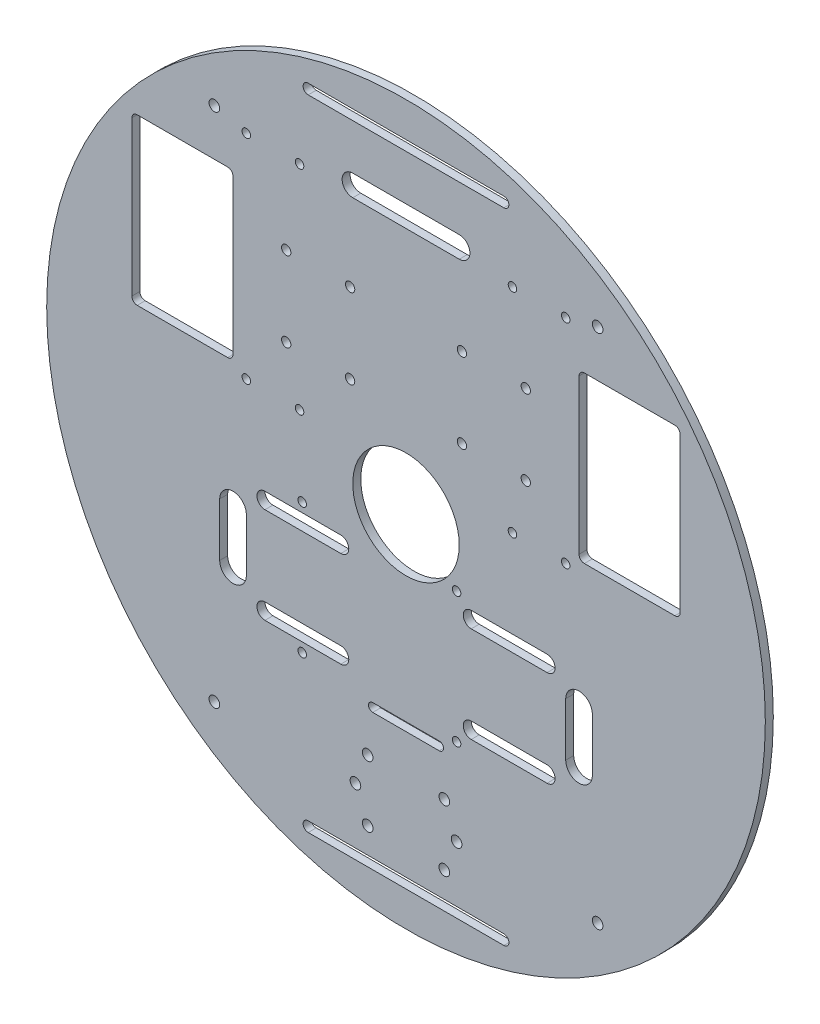
SolidWorks part; units mm, degrees
ref_plane "前视基准面" through (0, 0, 0) normal (0, 0, 1) x (1, 0, 0)
ref_plane "上视基准面" through (0, 0, 0) normal (0, 1, 0) x (1, 0, 0)
ref_plane "右视基准面" through (0, 0, 0) normal (1, 0, 0) x (0, 0, -1)
sketch "草图1" plane through (0, 0, 0) normal (0, 0, 1) x (1, 0, 0)
  line L0 (0, 135) -> (0, -135) construction
  line L1 (0, -96.9948) -> (84, 48.4974) construction
  line L2 (84, 48.4974) -> (-84, 48.4974) construction
  line L3 (-84, 48.4974) -> (0, -96.9948) construction
  line L4 (-103, 79.4974) -> (-65, 79.4974)
  line L5 (-103, 79.4974) -> (-103, 17.4974)
  line L6 (-103, 17.4974) -> (-65, 17.4974)
  line L7 (-65, 79.4974) -> (-65, 17.4974)
  line L8 (-103, 79.4974) -> (-65, 17.4974) construction
  line L9 (-103, 17.4974) -> (-65, 79.4974) construction
  line L10 (103, 79.4974) -> (65, 79.4974)
  line L11 (65, 79.4974) -> (65, 17.4974)
  line L12 (103, 79.4974) -> (65, 17.4974) construction
  line L13 (103, 17.4974) -> (65, 17.4974)
  line L14 (103, 17.4974) -> (65, 79.4974) construction
  line L15 (103, 79.4974) -> (103, 17.4974)
  line L17 (-14.4, -85.4948) -> (14.4, -85.4948) construction
  line L18 (-14.4, -85.4948) -> (-14.4, -108.4948) construction
  line L19 (-14.4, -108.4948) -> (14.4, -108.4948) construction
  line L20 (14.4, -85.4948) -> (14.4, -108.4948) construction
  line L21 (-14.4, -85.4948) -> (14.4, -108.4948) construction
  line L22 (-14.4, -108.4948) -> (14.4, -85.4948) construction
  line L29 (-45, 63.4974) -> (-21, 63.4974) construction
  line L30 (-45, 63.4974) -> (-45, 33.4974) construction
  line L31 (-45, 33.4974) -> (-21, 33.4974) construction
  line L32 (-21, 63.4974) -> (-21, 33.4974) construction
  line L33 (-45, 63.4974) -> (-21, 33.4974) construction
  line L34 (-45, 33.4974) -> (-21, 63.4974) construction
  circle A0 centre (0, 0) radius 135
  circle A1 centre (0, 0) radius 48.4974 construction
  circle A2 centre (-45, 63.4974) radius 1.75
  circle A3 centre (-21, 63.4974) radius 1.75
  circle A4 centre (-45, 33.4974) radius 1.75
  circle A5 centre (-21, 33.4974) radius 1.75
  circle A6 centre (45, 33.4974) radius 1.75
  circle A7 centre (21, 33.4974) radius 1.75
  circle A8 centre (21, 63.4974) radius 1.75
  circle A9 centre (45, 63.4974) radius 1.75
  circle A10 centre (19, -96.9948) radius 2
  circle A11 centre (14.4, -85.4948) radius 2
  circle A12 centre (14.4, -108.4948) radius 2
  circle A13 centre (-14.4, -85.4948) radius 2
  circle A14 centre (-14.4, -108.4948) radius 2
  circle A15 centre (-19, -96.9948) radius 2
  point P25 (0, 48.4974)
  point P26 (-33, 48.4974)
  point P30 (0, 48.4974)
  dimension "D1" = 270
  dimension "D9" = 3.5
  dimension "D10" = 3.5
  dimension "D11" = 3.5
  dimension "D12" = 3.5
  dimension "D14" = 19
  dimension "D2" = 38
  dimension "D3" = 62
  dimension "D4" = 84
  dimension "D5" = 70
  dimension "D6" = 28.8
  dimension "D7" = 24
  dimension "D8" = 30
  dimension "D13" = 23
extrude "凸台-拉伸1" add sketch "草图1" along normal blind 3 contours A0 A14 A9 A7 L10 L15 L13 L11 A2 A3 A4 A5 A6 A8 A10 A11 A12 A13 A15 region at (0, -4.2935, 0)
fillet "圆角1" radius 2 8 edges at (103, 79.4974, 1.5) (65, 79.4974, 1.5) (65, 17.4974, 1.5) (103, 17.4974, 1.5) (-65, 17.4974, 1.5) (-103, 17.4974, 1.5) (-103, 79.4974, 1.5) (-65, 79.4974, 1.5)
sketch "草图2" plane through (0, 0, 3) normal (0, 0, 1) x (1, 0, 0)
  line L0 (0, 97) -> (0, -96.9948) construction
  line L1 (-72, 97) -> (72, 97) construction
  line L2 (-72, 97) -> (-72, -97) construction
  line L3 (-72, -97) -> (72, -97) construction
  line L4 (72, 97) -> (72, -97) construction
  line L5 (-72, 97) -> (72, -97) construction
  line L6 (-72, -97) -> (72, 97) construction
  line L7 (24.5056, -55) -> (53, -55)
  line L8 (-53, -19) -> (-24.5056, -19)
  line L9 (-53, -19) -> (-53, -61) construction
  line L10 (-53, -61) -> (-24.5056, -61)
  line L11 (53, -19) -> (53, -61) construction
  line L12 (-53, -19) -> (53, -61) construction
  line L13 (-53, -61) -> (53, -19) construction
  line L14 (-53, -25) -> (-24.5056, -25)
  line L15 (-53, -25) -> (-53, -55) construction
  line L16 (-53, -55) -> (-24.5056, -55)
  line L17 (53, -25) -> (53, -55) construction
  line L18 (-53, -25) -> (53, -55) construction
  line L19 (-53, -55) -> (53, -25) construction
  line L20 (24.5056, -25) -> (53, -25)
  line L21 (24.5056, -19) -> (53, -19)
  line L22 (24.5056, -61) -> (53, -61)
  line L23 (40, 94) -> (40, 14) construction
  line L24 (-65, -30) -> (65, -30) construction
  line L25 (-65, -30) -> (-65, -50) construction
  line L26 (-65, -50) -> (65, -50) construction
  line L27 (65, -30) -> (65, -50) construction
  line L28 (-65, -30) -> (65, -50) construction
  line L29 (-65, -50) -> (65, -30) construction
  line L30 (-70, -30) -> (-60, -30) construction
  line L31 (-70, -30) -> (-70, -50)
  line L32 (-70, -50) -> (-60, -50) construction
  line L33 (-60, -30) -> (-60, -50)
  line L34 (-70, -30) -> (-60, -50) construction
  line L35 (-70, -50) -> (-60, -30) construction
  line L36 (60, -30) -> (70, -30) construction
  line L37 (60, -30) -> (60, -50)
  line L38 (60, -50) -> (70, -50) construction
  line L39 (70, -30) -> (70, -50)
  line L40 (60, -30) -> (70, -50) construction
  line L41 (60, -50) -> (70, -30) construction
  line L43 (35, -12.5) -> (-35, -12.5) construction
  line L44 (35, -12.5) -> (35, -67.5) construction
  line L45 (-42.5, -12) -> (42.5, -12) construction
  line L46 (-42.5, -12) -> (-42.5, -68) construction
  line L47 (-42.5, -68) -> (42.5, -68) construction
  line L48 (-135, 0) -> (135, 0) construction
  line L49 (-36.7556, -118.1) -> (36.7556, -121.9) construction
  line L50 (-36.7556, 121.9) -> (36.7556, 121.9)
  line L51 (-36.7556, 121.9) -> (-36.7556, 118.1) construction
  line L52 (-36.7556, 118.1) -> (36.7556, 118.1)
  line L53 (36.7556, 121.9) -> (36.7556, 118.1) construction
  line L54 (-36.7556, 121.9) -> (36.7556, 118.1) construction
  line L55 (-36.7556, 118.1) -> (36.7556, 121.9) construction
  line L56 (-36.7556, -121.9) -> (36.7556, -118.1) construction
  line L57 (36.7556, -121.9) -> (36.7556, -118.1) construction
  line L58 (-36.7556, -121.9) -> (-36.7556, -118.1) construction
  line L59 (-36.7556, -118.1) -> (36.7556, -118.1)
  line L60 (-36.7556, -121.9) -> (36.7556, -121.9)
  line L61 (-40, 94) -> (-40, 14) construction
  line L62 (-60, 94) -> (60, 94) construction
  line L63 (-60, 94) -> (-60, 14) construction
  line L64 (-60, 14) -> (60, 14) construction
  line L65 (60, 94) -> (60, 14) construction
  line L66 (-60, 94) -> (60, 14) construction
  line L67 (-60, 14) -> (60, 94) construction
  line L68 (42.5, -12) -> (42.5, -68) construction
  line L69 (-42.5, -12) -> (42.5, -68) construction
  line L70 (-42.5, -68) -> (42.5, -12) construction
  line L71 (-39, -15.5) -> (19, -15.5) construction
  line L72 (-39, -15.5) -> (-39, -64.5) construction
  line L73 (-39, -64.5) -> (19, -64.5) construction
  line L74 (19, -15.5) -> (19, -64.5) construction
  line L75 (-39, -15.5) -> (19, -64.5) construction
  line L76 (-39, -64.5) -> (19, -15.5) construction
  line L77 (35, -67.5) -> (-35, -67.5) construction
  line L78 (-35, -12.5) -> (-35, -67.5) construction
  line L79 (35, -12.5) -> (-35, -67.5) construction
  line L80 (35, -67.5) -> (-35, -12.5) construction
  line L81 (12.5, -70.7) -> (-12.5, -70.7)
  line L82 (12.5, -70.7) -> (12.5, -67.5) construction
  line L83 (12.5, -67.5) -> (-12.5, -67.5)
  line L84 (-12.5, -70.7) -> (-12.5, -67.5) construction
  line L85 (12.5, -70.7) -> (-12.5, -67.5) construction
  line L86 (12.5, -67.5) -> (-12.5, -70.7) construction
  line L87 (20, 101) -> (-20, 101)
  line L88 (20, 101) -> (20, 93) construction
  line L89 (20, 93) -> (-20, 93)
  line L90 (-20, 101) -> (-20, 93) construction
  line L91 (20, 101) -> (-20, 93) construction
  line L92 (20, 93) -> (-20, 101) construction
  circle A0 centre (0, 0) radius 20
  circle A1 centre (-72, 97) radius 2
  circle A2 centre (72, 97) radius 2
  circle A3 centre (72, -97) radius 2
  circle A4 centre (-72, -97) radius 2
  arc A5 (-53, -19) -> (-53, -25) centre (-53, -22) ccw
  arc A6 (-53, -55) -> (-53, -61) centre (-53, -58) ccw
  arc A7 (-24.5056, -19) -> (-24.5056, -25) centre (-24.5056, -22) cw
  arc A8 (-24.5056, -61) -> (-24.5056, -55) centre (-24.5056, -58) ccw
  arc A9 (53, -55) -> (53, -61) centre (53, -58) cw
  arc A10 (53, -19) -> (53, -25) centre (53, -22) cw
  arc A11 (24.5056, -61) -> (24.5056, -55) centre (24.5056, -58) cw
  arc A12 (24.5056, -19) -> (24.5056, -25) centre (24.5056, -22) ccw
  arc A13 (-70, -30) -> (-60, -30) centre (-65, -30) cw
  arc A14 (-70, -50) -> (-60, -50) centre (-65, -50) ccw
  arc A15 (60, -30) -> (70, -30) centre (65, -30) cw
  arc A16 (60, -50) -> (70, -50) centre (65, -50) ccw
  circle A17 centre (-60, 94) radius 1.6
  circle A18 centre (-60, 14) radius 1.6
  circle A19 centre (-40, 94) radius 1.6
  circle A20 centre (-40, 14) radius 1.6
  circle A21 centre (60, 14) radius 1.6
  circle A22 centre (60, 94) radius 1.6
  circle A23 centre (40, 94) radius 1.6
  circle A24 centre (40, 14) radius 1.6
  circle A25 centre (0, 0) radius 135 construction
  arc A26 (36.7556, 121.9) -> (36.7556, 118.1) centre (36.7556, 120) cw
  arc A27 (-36.7556, 121.9) -> (-36.7556, 118.1) centre (-36.7556, 120) ccw
  arc A28 (-36.7556, -121.9) -> (-36.7556, -118.1) centre (-36.7556, -120) cw
  arc A29 (36.7556, -121.9) -> (36.7556, -118.1) centre (36.7556, -120) ccw
  circle A30 centre (-39, -15.5) radius 1.6
  circle A31 centre (19, -15.5) radius 1.6
  circle A32 centre (-39, -64.5) radius 1.6
  circle A33 centre (19, -64.5) radius 1.6
  arc A34 (-12.5, -67.5) -> (-12.5, -70.7) centre (-12.5, -69.1) ccw
  arc A35 (12.5, -67.5) -> (12.5, -70.7) centre (12.5, -69.1) cw
  arc A36 (20, 101) -> (20, 93) centre (20, 97) cw
  arc A37 (-20, 101) -> (-20, 93) centre (-20, 97) ccw
  point P25 (0, 54)
  point P32 (0, -40)
  point P37 (-65, -40)
  point P38 (0, -40)
  point P39 (0, -40)
  point P52 (65, -40)
  point P61 (0, -40)
  point P77 (-10, -40)
  point P83 (0, 120)
  point P96 (0, -120)
  point P97 (0, -40)
  point P106 (-42.5, -40)
  point P111 (0, -40)
  point P116 (0, -69.1)
  dimension "D1" = 144
  dimension "D13" = 3.8
  dimension "D15" = 4
  dimension "D16" = 4
  dimension "D17" = 4
  dimension "D18" = 4
  dimension "D12" = 56
  dimension "D26" = 6
  dimension "D27" = 3
  dimension "D28" = 3
  dimension "D2" = 194
  dimension "D3" = 30
  dimension "D4" = 20
  dimension "D5" = 106
  dimension "D6" = 130
  dimension "D7" = 40
  dimension "D8" = 10
  dimension "D9" = 10
  dimension "D10" = 54
  dimension "D11" = 40
  dimension "D14" = 120
  dimension "D19" = 80
  dimension "D20" = 120
  dimension "D21" = 85
  dimension "D22" = 3.5
  dimension "D23" = 58
  dimension "D24" = 49
  dimension "D25" = 3.5
  dimension "D29" = 70
  dimension "D30" = 55
  dimension "D31" = 25
  dimension "D32" = 3.2
  dimension "D33" = 8
  dimension "D34" = 40
extrude "切除-拉伸1" cut sketch "草图2" against normal blind 10
sketch "草图3" plane through (0, 0, 3) normal (0, 0, 1) x (1, 0, 0)
  line L0 (0, 0) -> (0, -135) construction
  line L1 (0, 93) -> (0, 0) construction
  line L2 (35, -8.8786) -> (-35, -8.8786) construction
  line L3 (35, -8.8786) -> (35, -63.8786) construction
  line L4 (35, -63.8786) -> (-35, -63.8786) construction
  line L5 (-35, -8.8786) -> (-35, -63.8786) construction
  line L6 (35, -8.8786) -> (-35, -63.8786) construction
  line L7 (35, -63.8786) -> (-35, -8.8786) construction
  line L8 (-20, 93) -> (20, 93) construction
  circle A0 centre (0, 0) radius 135 construction
  point P6 (0, -36.3786)
  dimension "D1" = 55
  dimension "D2" = 70
  dimension "D3" = 93
